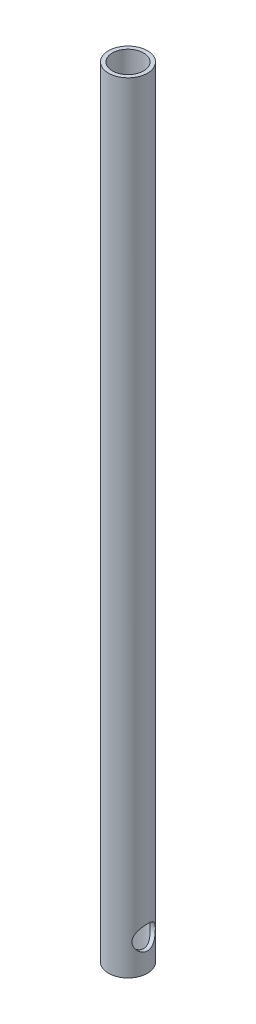
SolidWorks part; units mm, degrees
ref_plane "Front Plane" through (0, 0, 0) normal (0, 0, 1) x (1, 0, 0)
ref_plane "Top Plane" through (0, 0, 0) normal (0, 1, 0) x (1, 0, 0)
ref_plane "Right Plane" through (0, 0, 0) normal (1, 0, 0) x (0, 0, -1)
sketch "Sketch1" plane through (0, 0, 0) normal (0, 1, 0) x (1, 0, 0)
  circle A0 centre (0, 0) radius 2.5
  circle A1 centre (0, 0) radius 2
  dimension "D1" = 5
  dimension "D2" = 4
extrude "Boss-Extrude1" add sketch "Sketch1" along normal blind 100
sketch "Sketch2" plane through (0, 0, 0) normal (1, 0, 0) x (0, 0, -1)
  circle A0 centre (0, 4) radius 1.5
  dimension "D1" = 3
  dimension "D2" = 4
extrude "Cut-Extrude1" cut sketch "Sketch2" against normal blind 10 and the other way blind 10
